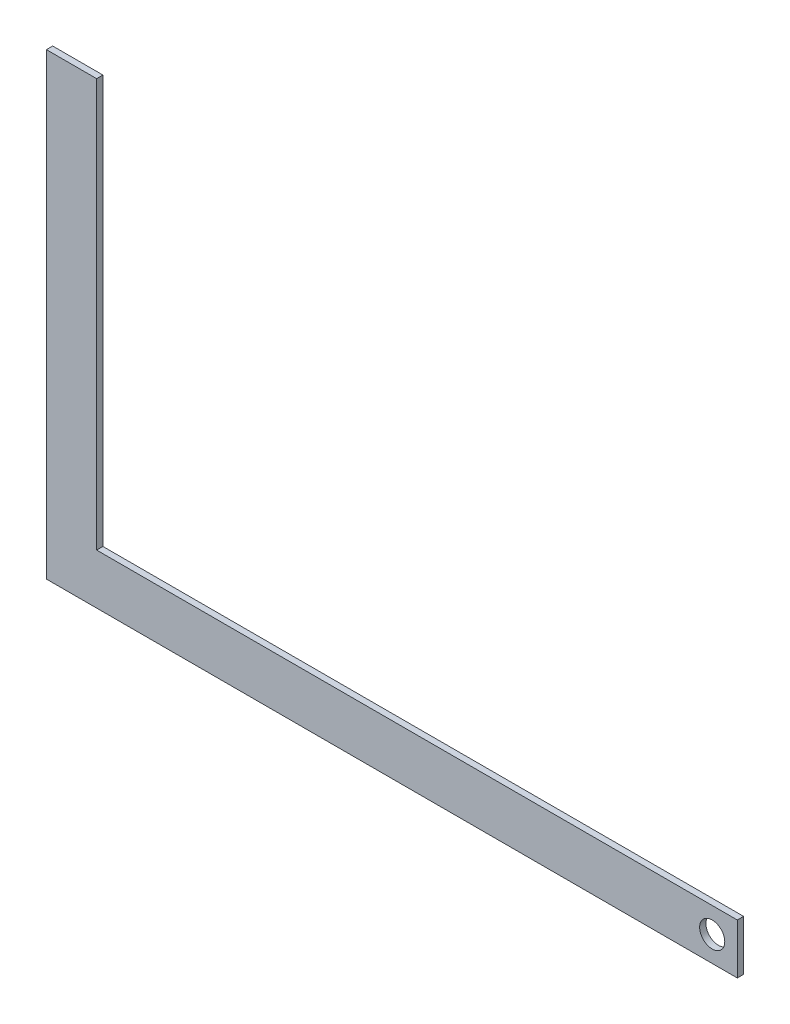
SolidWorks part; units mm, degrees
ref_plane "Front" through (0, 0, 0) normal (0, 0, 1) x (1, 0, 0)
ref_plane "Top" through (0, 0, 0) normal (0, 1, 0) x (1, 0, 0)
ref_plane "Right" through (0, 0, 0) normal (1, 0, 0) x (0, 0, -1)
sketch "Sketch1" plane through (0, 0, 0) normal (0, 0, 1) x (1, 0, 0)
  line L1 (0, 0) -> (349.25, 0)
  line L2 (0, 0) -> (0, 25.4)
  line L3 (0, 25.4) -> (349.25, 25.4)
  line L4 (349.25, 0) -> (349.25, 25.4)
  line L5 (0, 0) -> (349.25, 25.4) construction
  line L6 (0, 25.4) -> (349.25, 0) construction
  circle A0 centre (336.55, 12.7) radius 6.35
  point P4 (174.625, 12.7)
  dimension "D3" = 12.7
  dimension "D1" = 25.4
  dimension "D2" = 349.25
  dimension "D4" = 12.7
extrude "Boss-Extrude1" add sketch "Sketch1" along normal blind 3.175
sketch "Sketch2" plane through (0, 0, 3.175) normal (0, 0, 1) x (1, 0, 0)
  line L1 (0, 25.4) -> (25.4, 25.4)
  line L2 (0, 25.4) -> (0, 231.775)
  line L3 (0, 231.775) -> (25.4, 231.775)
  line L4 (25.4, 25.4) -> (25.4, 231.775)
  line L5 (0, 25.4) -> (25.4, 231.775) construction
  line L6 (0, 231.775) -> (25.4, 25.4) construction
  point P4 (12.7, 128.5875)
  dimension "D1" = 206.375
  dimension "D2" = 25.4
extrude "Boss-Extrude2" add sketch "Sketch2" against normal blind 3.175
